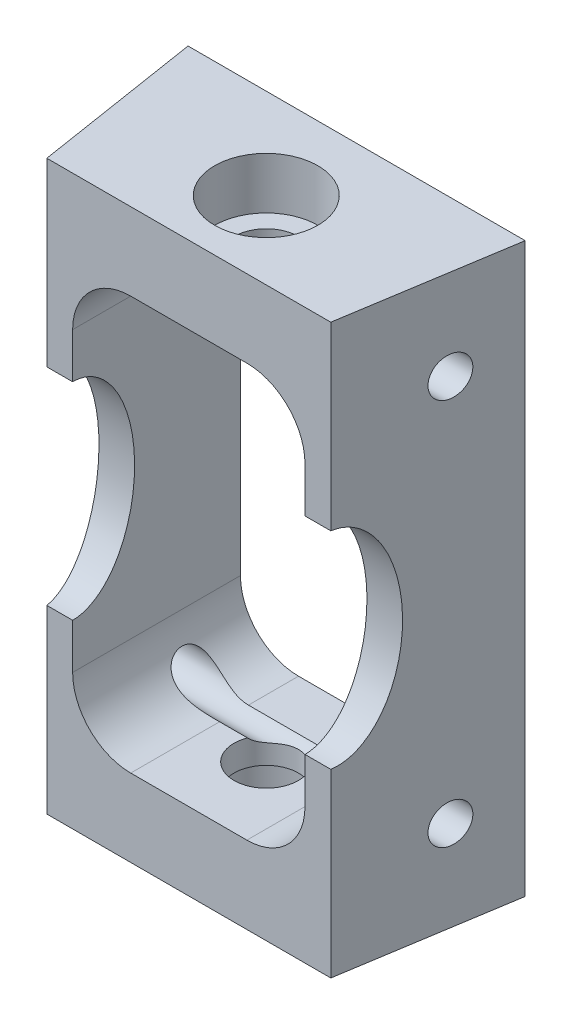
SolidWorks part; units mm, degrees
ref_plane "Front Plane" through (0, 0, 0) normal (0, 0, 1) x (1, 0, 0)
ref_plane "Top Plane" through (0, 0, 0) normal (0, 1, 0) x (1, 0, 0)
ref_plane "Right Plane" through (0, 0, 0) normal (1, 0, 0) x (0, 0, -1)
sketch "Sketch1" plane through (0, 0, 0) normal (0, 1, 0) x (1, 0, 0)
  line L0 (-11, 0) -> (11, 0)
  line L1 (0, 0) -> (0, 6) construction
  line L2 (-11.9503, 6) -> (-4, 6)
  line L3 (-11.9503, 6) -> (-11, 0)
  line L4 (11.9503, 6) -> (11, 0)
  line L5 (0, 3) -> (24.962, 3) construction
  line L6 (-11.9503, 6) -> (-7.6413, 10)
  line L7 (-7.6413, 10) -> (7.6413, 10) construction
  line L8 (7.6413, 10) -> (11.9503, 6)
  line L9 (4, 6) -> (11.9503, 6)
  line L10 (-4, 6) -> (4, 6) construction
  line L11 (-11.9503, 6) -> (-13.059, 13)
  line L12 (-13.059, 13) -> (2.6875, 13)
  line L14 (11.9503, 6) -> (13.059, 13)
  line L15 (13.059, 13) -> (-2.6875, 13)
  arc A0 (-7.6413, 10) -> (7.6413, 10) centre (0, 1.7684) cw
  circle A1 centre (0, 6) radius 4
  circle A3 centre (0, 6) radius 1.5
  point P4 (0, 0)
  point P9 (0, 6)
  point P10 (0, 2)
  point P19 (0, 10)
  point P20 (0, 5)
  point P22 (0, 0)
  point P25 (-11, 14)
  point P26 (0, 13)
  point P29 (10.5757, 14)
  point P30 (11, 14.5979)
  point P31 (9.5948, 8.1183)
  point P32 (7.848, 14)
  point P33 (2.6875, 14.1666)
  point P34 (0, 0)
  dimension "D3" = 8
  dimension "D5" = 3
  dimension "D4" = 3
  dimension "D7" = 3
  dimension "D1" = 81
  dimension "D2" = 22
  dimension "D6" = 6
extrude "Boss-Extrude1" add sketch "Sketch1" along normal blind 22 and the other way blind 22 contours A1 L2 L3 L0 L4 L9 | A1 L9 L8 A0 L6 L2 | L12 L11 L6 | L15 L8 L14 region at (-11.2318, 0, -3.0385) region at (-9.6264, 0, -7.8175) region at (-9.403, 0, -10.7896) region at (9.403, 0, -10.7896)
sketch "Sketch5" plane through (0, 0, 0) normal (0, 1, 0) x (1, 0, 0)
  circle A0 centre (0, 6) radius 4
  circle A1 centre (0, 6) radius 2.5
  dimension "D1" = 5
extrude "Boss-Extrude3" add sketch "Sketch5" along normal offset from surface 4 and the other way offset from surface 4 contours A0 A1 region at (-3.8869, 0, -6) up to face at (0, 22, -6.5) other way up to face at (0, -22, -6.5)
sketch "Sketch3" plane through (0, 0, 0) normal (1, 0, 0) x (0, 0, -1)
  line L0 (13, 0) -> (3, 0) construction
  line L3 (8, -15) -> (8, 15) construction
  line L7 (7.15, 0) -> (-7.15, 0) construction
  line L9 (13, -22) -> (13, 22) construction
  circle A0 centre (8, 15) radius 1.5
  circle A1 centre (8, -15) radius 1.5
  point P0 (5.0131, 0)
  point P3 (8, 0)
  point P10 (8, 0)
  dimension "D2" = 3
  dimension "D3" = 5
  dimension "D1" = 30
extrude "Cut-Extrude1" cut sketch "Sketch3" against normal blind 43 and the other way blind 43
sketch "Sketch4" plane through (0, 0, 0) normal (1, 0, 0) x (0, 0, -1)
  line L0 (12, 16.5) -> (6, 12)
  line L1 (12, -22) -> (12, 22) construction
  line L2 (6, -22) -> (6, 22) construction
  line L3 (6, 12) -> (6, 0)
  line L4 (6, 0) -> (12, 0)
  line L5 (12, 0) -> (12, 16.5)
  line L6 (13, 22) -> (0, 22) construction
  dimension "D1" = 5.5
  dimension "D2" = 10
extrude "Cut-Extrude2" [suppressed] cut sketch "Sketch4" against normal blind 43 and the other way blind 43
mirror "Mirror1" [suppressed] about plane through (0, 0, 0) normal (0, 1, 0)
sketch "Sketch6" plane through (0, 0, 0) normal (0, 0, 1) x (1, 0, 0)
  line L1 (-9, -16) -> (9, -16)
  line L2 (-9, -16) -> (-9, 16)
  line L3 (-9, 16) -> (9, 16)
  line L4 (9, -16) -> (9, 16)
  line L5 (-9, -16) -> (9, 16) construction
  line L6 (-9, 16) -> (9, -16) construction
  line L7 (-11, 22) -> (11, 22) construction
  line L9 (11, -22) -> (11, 22) construction
  arc A0 (-4.5, 16) -> (-9, 11.5) centre (-4.5, 11.5) ccw
  arc A1 (9, 11.5) -> (4.5, 16) centre (4.5, 11.5) ccw
  arc A2 (-9, -11.5) -> (-4.5, -16) centre (-4.5, -11.5) ccw
  arc A3 (4.5, -16) -> (9, -11.5) centre (4.5, -11.5) ccw
  point P0 (0, 0)
  point P6 (0, 0)
  point P7 (7.3262, 12)
  point P14 (0, 0)
  point P24 (0, 0)
  point P25 (0, 0)
  dimension "D3" = 9
  dimension "D1" = 2
  dimension "D2" = 6
extrude "Cut-Extrude3" cut sketch "Sketch6" against normal blind 24 and the other way blind 27 contours L1 A3 L4 A1 L3 A0 L2 A2 region at (0, 0, 0)
sketch "Sketch7" plane through (0, 0, 0) normal (1, 0, 0) x (0, 0, -1)
  line L7 (0, 14.1907) -> (0, -14.1907) construction
  line L8 (6.6, 0) -> (-6.6, 0) construction
  ellipse E0 centre (0, 0) end of major axis (0, 8) minor radius 4.8
  point P1 (0, 7.6278)
  point P7 (4.1446, 0)
  dimension "D1" = 4.8
  dimension "D2" = 8
extrude "Cut-Extrude4" cut sketch "Sketch7" against normal up to surface and the other way up to surface up to face at (-12.5047, 15, -9.5) other way up to face at (12.0295, 15, -6.5)
mirror "Mirror8" [suppressed] about plane through (0, 0, 0) normal (0, 1, 0)
